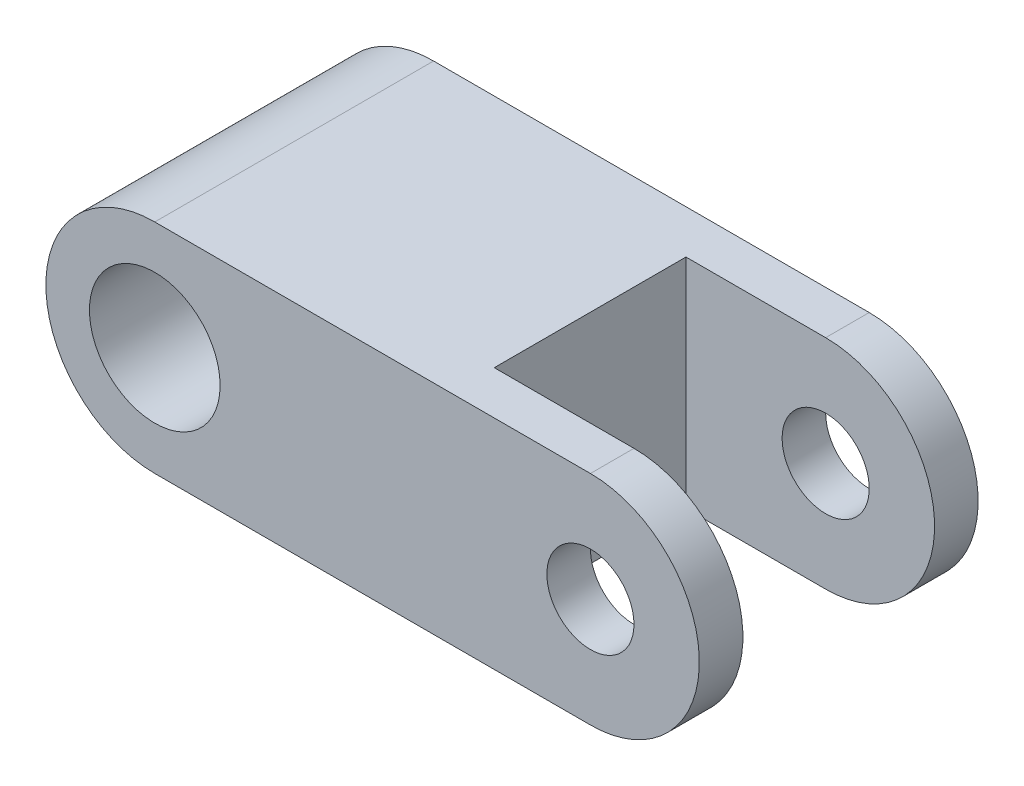
SolidWorks part; units mm, degrees
ref_plane "Front Plane" through (0, 0, 0) normal (0, 0, 1) x (1, 0, 0)
ref_plane "Top Plane" through (0, 0, 0) normal (0, 1, 0) x (1, 0, 0)
ref_plane "Right Plane" through (0, 0, 0) normal (1, 0, 0) x (0, 0, -1)
sketch "Sketch1" plane through (0, 0, 0) normal (0, 0, 1) x (1, 0, 0)
  line L0 (0, 0) -> (50, 0) construction
  line L1 (0, 12.5) -> (50, 12.5)
  line L2 (0, -12.5) -> (50, -12.5)
  arc A0 (0, 12.5) -> (0, -12.5) centre (0, 0) ccw
  arc A1 (50, -12.5) -> (50, 12.5) centre (50, 0) ccw
  circle A2 centre (0, 0) radius 7.5
  circle A3 centre (50, 0) radius 5
  point P3 (25, 0)
  dimension "D1" = 5
  dimension "D3" = 10
  dimension "D4" = 15
  dimension "D2" = 50
extrude "Boss-Extrude1" add sketch "Sketch1" along normal blind 32
sketch "Sketch2" plane through (0, 12.5, 0) normal (0, 1, 0) x (1, 0, 0)
  line L0 (62.5, -32) -> (62.5, 0) construction
  line L1 (62.5, -5) -> (33.9665, -5)
  line L2 (62.5, -5) -> (62.5, -27)
  line L3 (62.5, -27) -> (33.9665, -27)
  line L4 (33.9665, -5) -> (33.9665, -27)
  line L5 (50, -32) -> (50, 0) construction
  point P8 (50, -16)
  point P9 (33.9665, -16)
  dimension "D1" = 22
extrude "Cut-Extrude1" cut sketch "Sketch2" against normal up to next
